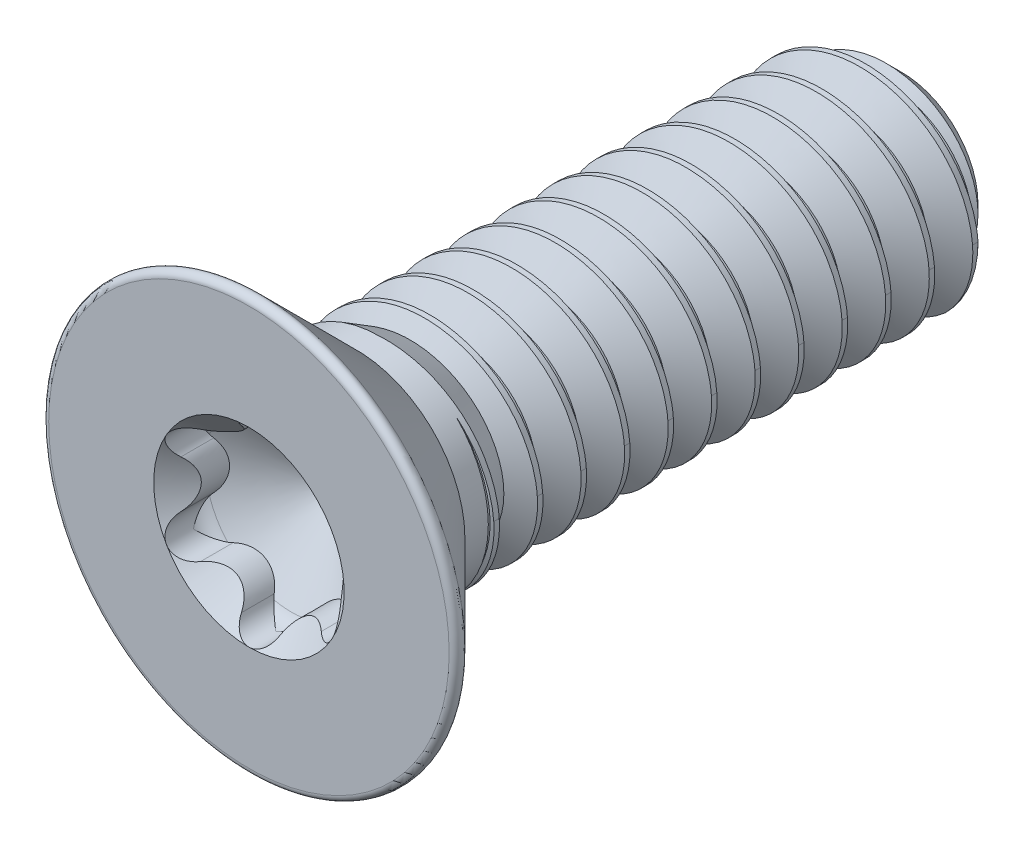
SolidWorks part; units mm, degrees
ref_plane "Front Plane" through (0, 0, 0) normal (0, 0, 1) x (1, 0, 0)
ref_plane "Top Plane" through (0, 0, 0) normal (0, 1, 0) x (1, 0, 0)
ref_plane "Right Plane" through (0, 0, 0) normal (1, 0, 0) x (0, 0, -1)
sketch "Sketch1" plane through (0, 0, 0) normal (1, 0, 0) x (0, 0, -1)
  line L0 (0, 0) -> (6, 0) construction
  line L1 (0, -1.9) -> (0, 1.9) construction
  line L2 (6, 1) -> (6, -1) construction
  line L3 (1.2, 0.7849) -> (1.2, -0.7849) construction
  line L5 (0.1024, 1.8824) -> (1.2, 0.7849) construction
  line L6 (6, 1) -> (0.9849, 1) construction
  line L7 (5.975, 1.0433) -> (6.175, 0.6969) construction
  line L8 (6.175, 0.6969) -> (6.375, 1.0433) construction
  line L9 (6.375, 1.0433) -> (5.975, 1.0433) construction
  line L10 (6, -1) -> (0.9849, -1) construction
  line L11 (6.175, 0.7402) -> (6.175, 0.6969) construction
  line L12 (6.175, 1.0433) -> (6.175, 1) construction
  line L13 (6.35, 1) -> (6, 1) construction
  line L14 (6.15, 0.7402) -> (6.2, 0.7402) construction
  line L15 (6.175, 1.0217) -> (5.9875, 1.0217) construction
  line L16 (6.175, 1.0217) -> (6.3625, 1.0217) construction
  line L17 (1.2, 0.7849) -> (6, 0.7849) construction
  line L18 (0.1024, -1.8824) -> (1.2, -0.7849) construction
  line L19 (0, -1.9) -> (1.2, -1.9) construction
  line L20 (1.2, -1.9) -> (1.2, 1.9) construction
  line L21 (1.2, 1.9) -> (0, 1.9) construction
  arc A0 (0, 1.84) -> (0.1024, 1.8824) centre (0.06, 1.84) cw
  arc A1 (0, -1.84) -> (0.1024, -1.8824) centre (0.06, -1.84) ccw
  point P7 (1.2, 0)
  point P17 (1.2, 0.7849)
  point P18 (0, 1.9)
  point P29 (5, -1)
  dimension "D3" = 0.06
  dimension "Length" = 6
  dimension "Thread Size" = 2
  dimension "Head Diameter" = 3.8
  dimension "Head Height" = 1.2
  dimension "Thread Pitch" = 0.4
  dimension "D2" = 0.05
  dimension "D1" = 1
  dimension "Countersink Angle" = 90
sketch "Sketch2" plane through (0, 0, 0) normal (0, 0, 1) x (1, 0, 0)
  line L0 (0, -1.9) -> (0, 1.9) construction
  circle A0 centre (0, 0) radius 1
  circle A1 centre (0, 0) radius 1.9 construction
  circle A2 centre (0, 0) radius 0.875 construction
  point P8 (0, -0.875)
  dimension "D1" = 1.75
extrude "Boss-Extrude1" add sketch "Sketch2" against normal up to vertex (6 mm away) up to point (0, 0, -6)
chamfer "Chamfer1" distance 0.3 angle 45 1 edges at (1, 0, -6)
sketch "Sketch3" plane through (0, 0, 0) normal (1, 0, 0) x (0, 0, -1)
  line L0 (0.1024, 1.8824) -> (1.2, 0.7849) construction
  line L1 (0.1024, 1.8824) -> (1.2, 0.7849)
  line L2 (1.2, 0.7849) -> (1.2, 0)
  line L3 (1.2, 0.7849) -> (1.2, -0.7849) construction
  line L4 (1.2, 0) -> (0, 0)
  line L5 (0, 1.84) -> (0, 0)
  arc A0 (0.1024, 1.8824) -> (0, 1.84) centre (0.06, 1.84) ccw construction
  arc A1 (0.1024, 1.8824) -> (0, 1.84) centre (0.06, 1.84) ccw
revolve "Revolve1" add sketch "Sketch3" angle 360 about L4
sketch "Sketch4" plane through (0, 0, 0) normal (1, 0, 0) x (0, 0, -1)
  line L0 (1.2, 0.7849) -> (1.9849, 0)
  line L1 (0, 0) -> (6, 0) construction
  line L2 (1.9849, 0) -> (1.2, 0)
  line L6 (1.2, 0) -> (1.2, 0.7849)
revolve "Revolve2" add sketch "Sketch4" angle 360 about L2
ref_plane "Plane1" through (0, 0, 22.448) normal (0, 0, -1) x (-1, 0, 0)
sketch "Sketch5" plane through (0, 0, 0) normal (0, 0, 1) x (1, 0, 0)
  line L0 (0, 0.875) -> (0, 0) construction
  line L1 (0, 0) -> (-0.875, 0) construction
  line L2 (-0.7578, 0.4375) -> (0, 0) construction
  line L3 (0, 0) -> (-0.8525, -0.4922) construction
  line L4 (-0.7578, 0.4375) -> (-0.8525, 0.4922)
  line L5 (-0.8525, -0.4922) -> (-0.6631, -0.3828) construction
  line L6 (-0.7578, -0.4375) -> (-0.8525, -0.4922)
  line L7 (-0.6631, -0.3828) -> (-0.7578, -0.4375) construction
  circle A0 centre (0, 0) radius 0.875 construction
  circle A1 centre (0, 0) radius 0.875 construction
  circle A2 centre (0, 0) radius 0.7656 construction
  circle A3 centre (0, 0) radius 0.6563 construction
  arc A4 (-0.8525, 0.4922) -> (-0.8525, -0.4922) centre (0, 0) ccw
  arc A5 (-0.734, 0.2177) -> (-0.7578, 0.4375) centre (-0.5956, 0.3439) cw
  arc A6 (-0.734, -0.2177) -> (-0.7578, -0.4375) centre (-0.5956, -0.3439) ccw
  ellipse E1 centre (-0.875, 0) end of major axis (-0.875, -0.2848) minor radius 0.2187 (-0.734, -0.2177) -> (-0.734, 0.2177) ccw
  dimension "D2" = 1.5312
  dimension "D3" = 1.3125
  dimension "D1" = 30
sketch "Sketch6" plane through (0, 0, 0) normal (1, 0, 0) x (0, 0, -1)
  line L0 (0, 0.875) -> (0.2474, 0.875)
  line L2 (0, 0) -> (0.81, 0)
  line L3 (0, 0.7656) -> (0, -0.7656) construction
  line L4 (0.81, 0) -> (0.81, -1.1749) construction
  line L6 (0, 0.875) -> (0, 0)
  line L7 (0.1024, -1.8824) -> (1.2, -0.7849) construction
  line L8 (0.81, 0) -> (0.81, 0.1215)
  line L9 (0.3931, 0.7939) -> (0.81, 0.1215)
  arc A2 (0.2474, 0.875) -> (0.3931, 0.7939) centre (0.2474, 0.7036) cw
  point P9 (0.3429, 0.875)
  dimension "D4" = 0.1714
  dimension "D1" = 0.3429
  dimension "D2" = 0.81
  dimension "D3" = 0.1215
revolve "Cut-Revolve1" cut sketch "Sketch6" angle 360 about L2
extrude "Boss-Extrude2" add sketch "Sketch5" against normal up to next contours E1 A5 L4 A4 L6 A6
pattern_circular "CirPattern1" count 6 over 360 about axis through (0, 0, 0) along (0, 0, -1) of "Boss-Extrude2"
sketch "Sketch7" plane through (0, 0, 0) normal (0, 0, 1) x (1, 0, 0)
  circle A0 centre (0, 0) radius 0.875 construction
  circle A1 centre (0, 0) radius 0.875
extrude "Cut-Extrude1" cut sketch "Sketch7" against normal up to next (0.81 mm away) draft 45
ref_plane "Plane2" through (0, 0, -1.2) normal (0, 0, -1) x (-1, 0, 0)
split "Split1" trim tools "Plane2" bodies to split 109 resulting bodies 125 126
sketch "Sketch8" plane through (0, 0, 0) normal (1, 0, 0) x (0, 0, -1)
  line L0 (5.9875, 1.0217) -> (6.3625, 1.0217)
  line L1 (6.3625, 1.0217) -> (6.2, 0.7402)
  line L2 (6.2, 0.7402) -> (6.15, 0.7402)
  line L3 (6.15, 0.7402) -> (5.9875, 1.0217)
sketch "Sketch9" plane through (0, 0, -6) normal (0, 0, -1) x (-1, 0, 0)
  circle A0 centre (0, 0) radius 1 construction
  circle A1 centre (0, 0) radius 1
curve "Helix/Spiral1" pitch 0.4 height 6 radius 1 centre (0, 0, -6) axis (0, 0, 1) start towards (0, 1, 0)
sweep "Cut-Sweep1" cut profiles "Sketch8" path "Helix/Spiral1" align with end faces yes
sketch "Sketch10" plane through (0, 0, -1.2) normal (0, 0, -1) x (-1, 0, 0)
  circle A0 centre (0, 0) radius 1 construction
  circle A4 centre (0, 0) radius 1
extrude "Boss-Extrude3" add sketch "Sketch10" along normal up to next (4.8 mm away) draft 30
sketch "Sketch11" plane through (0, 0, 0) normal (1, 0, 0) x (0, 0, -1)
  point P0 (0, -0.875)
ref_axis "Axis1" through (0, 0, -6.4476) along (0, 0, 1)
equation "\"D4@Helix/Spiral1\" = \"Thread Pitch@Sketch1\""
equation "\"D3@Helix/Spiral1\"=\"Length@Sketch1\""
equation "\"D2@Sketch5\" = \"D1@Sketch2\" * 0.875"
equation "\"D3@Sketch5\" = \"D1@Sketch2\" * 0.75"
equation "\"D1@Chamfer1\"=\"D4@Helix/Spiral1\"*.75"
equation "\"D2@Sketch1\" = \"Thread Pitch@Sketch1\" / 8"
equation "\"D1@Sketch1\" = \"Thread Pitch@Sketch1\" * 2.5"
equation "\"D1@Sketch6\" = \"Head Height@Sketch1\" / 3.5"
equation "\"D2@Sketch6\" = \"Head Height@Sketch1\" * .675"
equation "\"D3@Sketch1\"=\"Head Height@Sketch1\"*.05"
equation "\"D3@Sketch6\" = \"D2@Sketch6\" * .15"
equation "\"D4@Sketch6\" = \"D1@Sketch6\" * .5"
